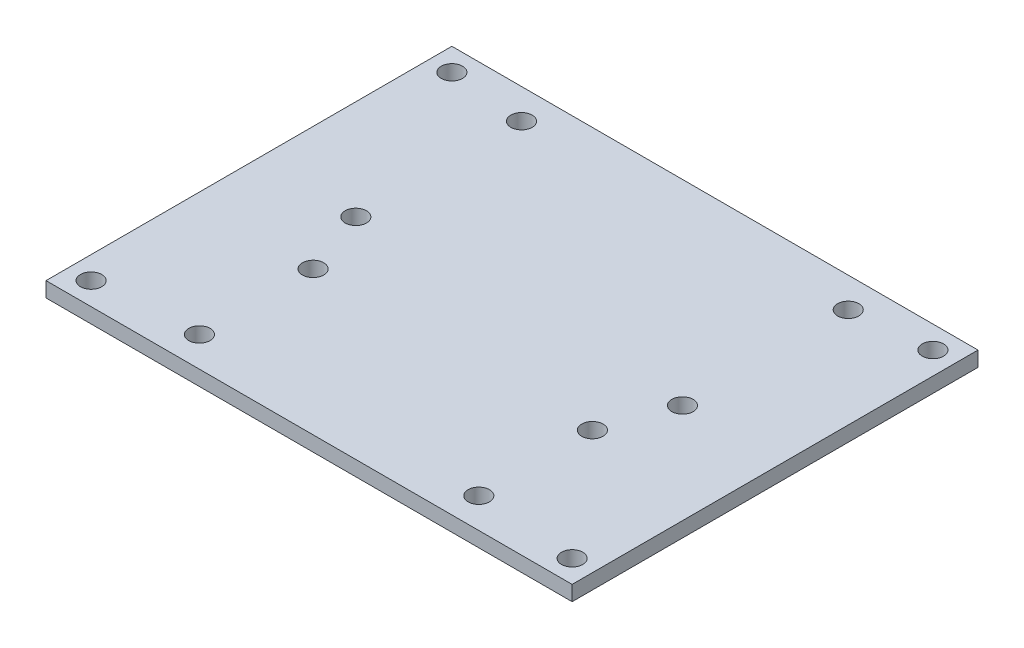
SolidWorks part; units mm, degrees
material "6061 Alloy"
ref_plane "Front Plane" through (0, 0, 0) normal (0, 0, 1) x (1, 0, 0)
ref_plane "Top Plane" through (0, 0, 0) normal (0, 1, 0) x (1, 0, 0)
ref_plane "Right Plane" through (0, 0, 0) normal (1, 0, 0) x (0, 0, -1)
sketch "Sketch1" plane through (0, 0, 0) normal (0, 1, 0) x (1, 0, 0)
  line L0 (-55.5625, 42.8625) -> (55.5625, 42.8625)
  line L1 (-50.8, -38.1) -> (50.8, -38.1) construction
  line L2 (-50.8, -38.1) -> (-50.8, 38.1) construction
  line L3 (-50.8, 38.1) -> (50.8, 38.1) construction
  line L4 (50.8, -38.1) -> (50.8, 38.1) construction
  line L5 (-50.8, -38.1) -> (50.8, 38.1) construction
  line L6 (-50.8, 38.1) -> (50.8, -38.1) construction
  line L7 (55.5625, -42.8625) -> (55.5625, 42.8625)
  line L8 (-55.5625, -42.8625) -> (55.5625, -42.8625)
  line L9 (-55.5625, -42.8625) -> (-55.5625, 42.8625)
  point P0 (0, 0)
  dimension "D1" = 101.6
  dimension "D2" = 76.2
  dimension "D3" = 4.7625
extrude "Boss-Extrude1" add sketch "Sketch1" along normal blind 3.175
hole_wizard "M3 Clearance Hole1" positions "3DSketch1" profile "Sketch2" hole size "M3" standard "ANSI Metric" end condition through all
sketch3d "3DSketch1"
  point P0 (-50.8, 0, 38.1)
  point P3 (50.8, 0, 38.1)
  point P6 (-50.8, 0, -38.1)
  point P9 (50.8, 0, -38.1)
sketch "Sketch2" plane through (-50.8, 0, 38.1) normal (1, 0, 0) x (0, 0, -1)
  line L0 (0, 0) -> (0, 3.175)
  line L1 (0, 3.175) -> (2.25, 3.175)
  line L2 (2.25, 3.175) -> (2.25, 0)
  line L5 (2.25, 0) -> (0, 0)
  line L11 (0, -6.35) -> (0, 107.95) construction
  dimension "Thru Hole Dia." = 4.5
  dimension "Thru Hole Depth" = 3.175
sketch "Sketch3" plane through (0, 3.175, 0) normal (0, 1, 0) x (1, 0, 0)
  line L0 (0, 19.0125) -> (0, -24.5125) construction
  line L1 (-34.5, 36.5125) -> (34.5, 36.5125) construction
  line L2 (-34.5, 36.5125) -> (-34.5, 1.5125) construction
  line L3 (-34.5, 1.5125) -> (34.5, 1.5125) construction
  line L4 (34.5, 36.5125) -> (34.5, 1.5125) construction
  line L5 (-34.5, 36.5125) -> (34.5, 1.5125) construction
  line L6 (-34.5, 1.5125) -> (34.5, 36.5125) construction
  line L7 (-29.5, -36.5125) -> (29.5, -36.5125) construction
  line L8 (-29.5, -36.5125) -> (-29.5, -12.5125) construction
  line L9 (-29.5, -12.5125) -> (29.5, -12.5125) construction
  line L10 (29.5, -36.5125) -> (29.5, -12.5125) construction
  line L11 (-29.5, -36.5125) -> (29.5, -12.5125) construction
  line L12 (-29.5, -12.5125) -> (29.5, -36.5125) construction
  line L13 (-55.5625, -42.8625) -> (55.5625, -42.8625) construction
  line L14 (55.5625, 42.8625) -> (-55.5625, 42.8625) construction
  point P0 (0, 19.0125)
  point P5 (0, -24.5125)
  dimension "D1" = 69
  dimension "D2" = 35
  dimension "D3" = 59
  dimension "D4" = 24
  dimension "D5" = 6.35
  dimension "D6" = 6.35
hole_wizard "M3 Clearance Hole2" positions "3DSketch2" profile "Sketch4" hole size "M3" standard "ANSI Metric" end condition through all
sketch3d "3DSketch2"
  point P0 (-29.5, 3.175, 36.5125)
  point P3 (-29.5, 3.175, 12.5125)
  point P6 (29.5, 3.175, 12.5125)
  point P9 (29.5, 3.175, 36.5125)
  point P12 (34.5, 3.175, -1.5125)
  point P15 (34.5, 3.175, -36.5125)
  point P18 (-34.5, 3.175, -36.5125)
  point P24 (-34.5, 3.175, -1.5125)
sketch "Sketch4" plane through (-29.5, 3.175, 36.5125) normal (1, 0, 0) x (0, 0, 1)
  line L0 (0, 0) -> (0, 3.175)
  line L1 (0, 3.175) -> (2.25, 3.175)
  line L2 (2.25, 3.175) -> (2.25, 0)
  line L5 (2.25, 0) -> (0, 0)
  line L11 (0, -6.35) -> (0, 107.95) construction
  dimension "Thru Hole Dia." = 4.5
  dimension "Thru Hole Depth" = 3.175
equation "\"D5@Sketch3\"=\"D6@Sketch3\""
